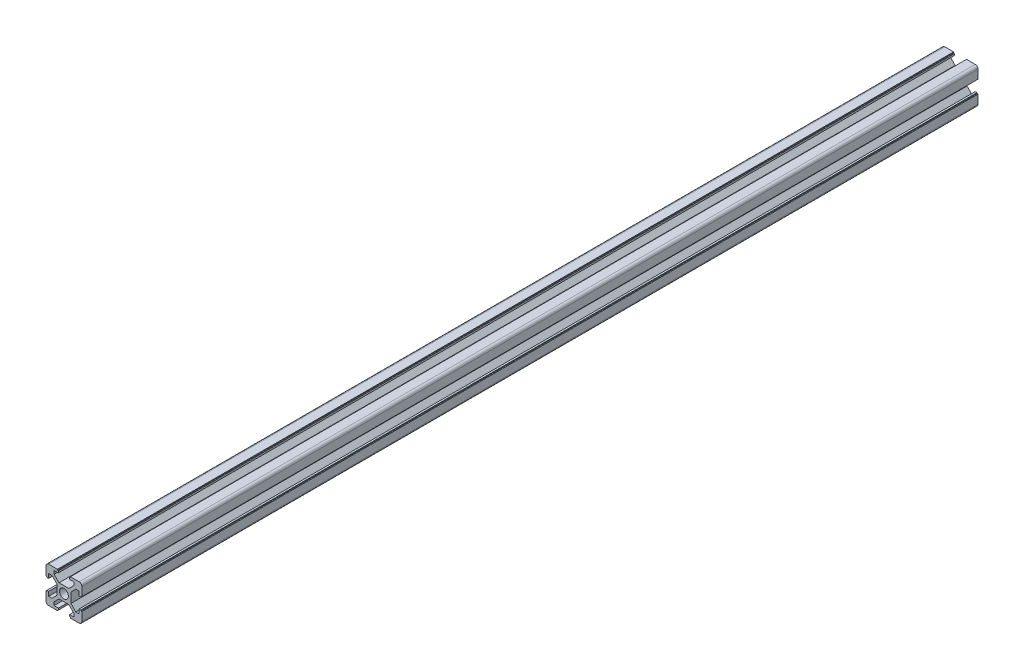
SolidWorks part; units mm, degrees
material "6061 合金"
ref_plane "前视基准面" through (0, 0, 0) normal (0, 0, 1) x (1, 0, 0)
ref_plane "上视基准面" through (0, 0, 0) normal (0, 1, 0) x (1, 0, 0)
ref_plane "右视基准面" through (0, 0, 0) normal (1, 0, 0) x (0, 0, -1)
sketch "草图1" plane through (0, 0, 0) normal (0, 0, 1) x (1, 0, 0)
  line B0 (8.5, 10) -> (3.6, 10)
  line B1 (10, 3.6) -> (10, 8.5)
  line B2 (9.5, 3.6) -> (10, 3.6)
  line B3 (9.5, 3.1) -> (9.5, 3.6)
  line B4 (8.5, 3.1) -> (9.5, 3.1)
  line B5 (8.5, 5.5) -> (8.5, 3.1)
  line B6 (6.65, 5.5) -> (8.5, 5.5)
  line B7 (3.9, 2.75) -> (6.65, 5.5)
  line B8 (3.9, -2.75) -> (3.9, 2.75)
  line B9 (6.65, -5.5) -> (3.9, -2.75)
  line B10 (8.5, -5.5) -> (6.65, -5.5)
  line B11 (8.5, -3.1) -> (8.5, -5.5)
  line B12 (9.5, -3.1) -> (8.5, -3.1)
  line B13 (9.5, -3.6) -> (9.5, -3.1)
  line B14 (10, -3.6) -> (9.5, -3.6)
  line B15 (10, -8.5) -> (10, -3.6)
  line B16 (3.6, -10) -> (8.5, -10)
  line B17 (3.6, -9.5) -> (3.6, -10)
  line B18 (3.1, -9.5) -> (3.6, -9.5)
  line B19 (3.1, -8.5) -> (3.1, -9.5)
  line B20 (5.5, -8.5) -> (3.1, -8.5)
  line B21 (5.5, -6.65) -> (5.5, -8.5)
  line B22 (2.75, -3.9) -> (5.5, -6.65)
  line B23 (-2.75, -3.9) -> (2.75, -3.9)
  line B24 (-5.5, -6.65) -> (-2.75, -3.9)
  line B25 (-5.5, -8.5) -> (-5.5, -6.65)
  line B26 (-3.1, -8.5) -> (-5.5, -8.5)
  line B27 (-3.1, -9.5) -> (-3.1, -8.5)
  line B28 (-3.6, -9.5) -> (-3.1, -9.5)
  line B29 (-3.6, -10) -> (-3.6, -9.5)
  line B30 (-8.5, -10) -> (-3.6, -10)
  line B31 (-10, -3.6) -> (-10, -8.5)
  line B32 (-9.5, -3.6) -> (-10, -3.6)
  line B33 (-9.5, -3.1) -> (-9.5, -3.6)
  line B34 (-8.5, -3.1) -> (-9.5, -3.1)
  line B35 (-8.5, -5.5) -> (-8.5, -3.1)
  line B36 (-6.65, -5.5) -> (-8.5, -5.5)
  line B37 (-3.9, -2.75) -> (-6.65, -5.5)
  line B38 (-3.9, 2.75) -> (-3.9, -2.75)
  line B39 (-6.65, 5.5) -> (-3.9, 2.75)
  line B40 (-8.5, 5.5) -> (-6.65, 5.5)
  line B41 (-8.5, 3.1) -> (-8.5, 5.5)
  line B42 (-9.5, 3.1) -> (-8.5, 3.1)
  line B43 (-9.5, 3.6) -> (-9.5, 3.1)
  line B44 (-10, 3.6) -> (-9.5, 3.6)
  line B45 (-10, 8.5) -> (-10, 3.6)
  line B46 (-3.6, 10) -> (-8.5, 10)
  line B47 (-3.6, 9.5) -> (-3.6, 10)
  line B48 (-3.1, 9.5) -> (-3.6, 9.5)
  line B49 (-3.1, 8.5) -> (-3.1, 9.5)
  line B50 (-5.5, 8.5) -> (-3.1, 8.5)
  line B51 (-5.5, 6.65) -> (-5.5, 8.5)
  line B52 (-2.75, 3.9) -> (-5.5, 6.65)
  line B53 (2.75, 3.9) -> (-2.75, 3.9)
  line B54 (5.5, 6.65) -> (2.75, 3.9)
  line B55 (5.5, 8.5) -> (5.5, 6.65)
  line B56 (3.1, 8.5) -> (5.5, 8.5)
  line B57 (3.1, 9.5) -> (3.1, 8.5)
  line B58 (3.6, 9.5) -> (3.1, 9.5)
  line B59 (3.6, 10) -> (3.6, 9.5)
  arc B60 (-2.5, 0) -> (2.5, 0) centre (0, 0) ccw
  arc B61 (2.5, 0) -> (-2.5, 0) centre (0, 0) ccw
  arc B62 (10, 8.5) -> (8.5, 10) centre (8.5, 8.5) ccw
  arc B63 (8.5, -10) -> (10, -8.5) centre (8.5, -8.5) ccw
  arc B64 (-10, -8.5) -> (-8.5, -10) centre (-8.5, -8.5) ccw
  arc B65 (-8.5, 10) -> (-10, 8.5) centre (-8.5, 8.5) ccw
sketch_block_instance "2020铝型材-1"
sketch_block "2020铝型材"
extrude "凸台-拉伸1" add sketch "草图1" along normal blind 500
sketch "草图2" plane through (0, 3.9, 0) normal (0, 1, 0) x (1, 0, 0)
  line L0 (0, -375) -> (0, -125) construction
  line L1 (2.75, -500) -> (-2.75, -500) construction
  circle A0 centre (0, -250) radius 2.05
  circle A1 centre (0, -125) radius 2.05
  circle A2 centre (0, -375) radius 2.05
  dimension "D1" = 4.1
  dimension "D2" = 4.1
  dimension "D3" = 250
  dimension "D4" = 250
extrude "切除-拉伸1" cut sketch "草图2" against normal through all
